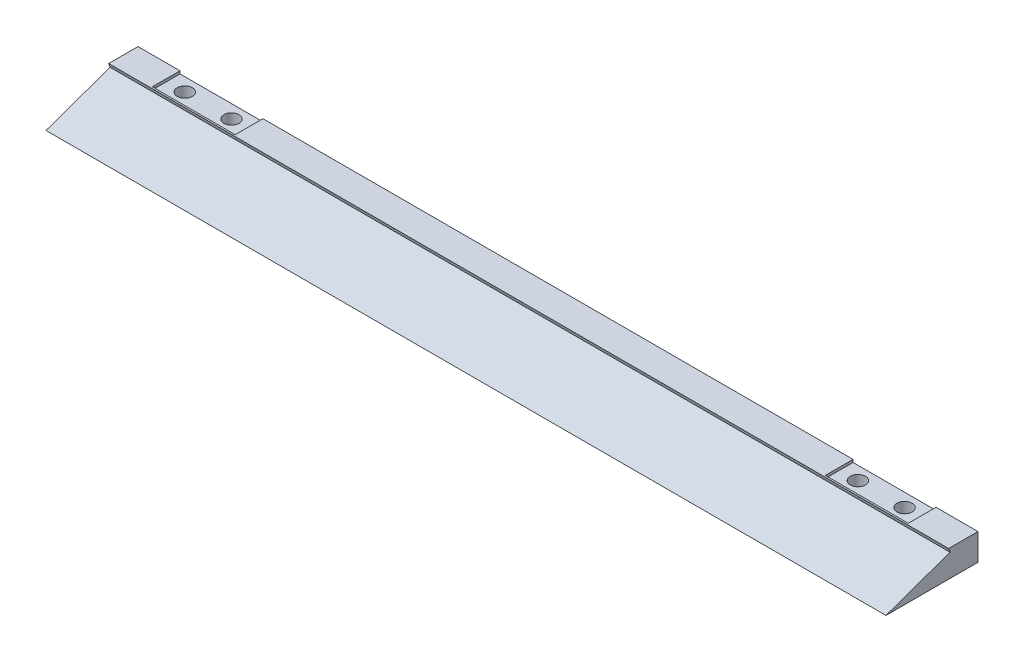
SolidWorks part; units mm, degrees
material "1023 Carbon Steel Sheet (SS)"
ref_plane "Front Plane" through (0, 0, 0) normal (0, 0, 1) x (1, 0, 0)
ref_plane "Top Plane" through (0, 0, 0) normal (0, 1, 0) x (1, 0, 0)
ref_plane "Right Plane" through (0, 0, 0) normal (1, 0, 0) x (0, 0, -1)
sketch "Sketch1" plane through (0, 0, 0) normal (0, 1, 0) x (1, 0, 0)
  line L1 (-100, -15) -> (100, -15)
  line L2 (-100, -15) -> (-100, 15)
  line L3 (-100, 15) -> (100, 15)
  line L4 (100, -15) -> (100, 15)
  line L5 (-100, -15) -> (100, 15) construction
  line L6 (-100, 15) -> (100, -15) construction
  point P0 (0, 0)
  dimension "D1" = 200
  dimension "D2" = 30
extrude "Base" add sketch "Sketch1" along normal blind 6.35
ref_plane "Midplane" through (0, 0, 0) normal (1, 0, 0) x (0, 0, -1)
sketch "Sketch2" plane through (100, 0, 0) normal (1, 0, 0) x (0, 0, -1)
  line L0 (-6.9075, 0) -> (11, 6.35)
  line L1 (-15, 0) -> (15, 0) construction
  line L2 (-15, 6.35) -> (15, 6.35) construction
  line L3 (11, 6.35) -> (11, 0)
  line L4 (11, 0) -> (-6.9075, 0)
  line L5 (15, 6.35) -> (15, 0) construction
  line L7 (11, 6.35) -> (-15, 6.35)
  line L8 (-15, 6.35) -> (-15, 0)
  line L9 (-15, 0) -> (-6.9075, 0)
  line L10 (8.3421, 5.4075) -> (8.0079, 6.35)
  line M3 (-15, 0) -> (15, 0)
  line M5 (15, 6.35) -> (-15, 6.35)
  line M6 (-15, 6.35) -> (-15, 0)
  dimension "D1" = 19
  dimension "D2" = 4
  dimension "D3" = 1
extrude "WedgeCut" cut sketch "Sketch2" against normal up to next contours L0 M3 M5 M6 region at (100, 3.7005, 5.8885)
sketch "Sketch3" plane through (0, 6.35, 0) normal (0, 1, 0) x (1, 0, 0)
  line L0 (-100, 15) -> (-100, 8.0079) construction
  line L1 (-90, 8.396) -> (-70.254, 8.396)
  line L2 (-90, 8.396) -> (-90, 15)
  line L3 (-90, 15) -> (-70.254, 15)
  line L4 (-70.254, 8.396) -> (-70.254, 15)
  line L5 (-90, 8.396) -> (-70.254, 15) construction
  line L6 (-90, 15) -> (-70.254, 8.396) construction
  line L7 (70.254, 15) -> (90, 15)
  line L8 (70.254, 15) -> (70.254, 8.396)
  line L9 (70.254, 8.396) -> (90, 8.396)
  line L10 (90, 15) -> (90, 8.396)
  line L11 (70.254, 15) -> (90, 8.396) construction
  line L12 (70.254, 8.396) -> (90, 15) construction
  line L13 (100, 15) -> (-100, 15) construction
  line L14 (100, 8.0079) -> (100, 15) construction
  point P0 (-80.127, 11.698)
  point P5 (80.127, 11.698)
  dimension "D1" = 6.604
  dimension "D2" = 19.746
  dimension "D3" = 10
  dimension "D4" = 19.746
  dimension "D5" = 10
  dimension "D6" = 6.604
extrude "Hinge Cutout" cut sketch "Sketch3" against normal blind 0.635
sketch "Sketch4" plane through (0, 5.715, 0) normal (0, 1, 0) x (1, 0, 0)
  line L0 (90, 15) -> (70.254, 15) construction
  circle A0 centre (74.5644, 11.825) radius 1.8034
  circle A1 centre (85.6896, 11.825) radius 1.8034
  point P6 (80.127, 15)
  dimension "D5" = 3.6068
  dimension "D6" = 3.6068
  dimension "D1" = 5.5626
  dimension "D2" = 5.5626
  dimension "D3" = 3.175
  dimension "D4" = 3.175
extrude "Hinge Hole Cut" cut sketch "Sketch4" against normal up to next
sketch "Sketch5" plane through (0, 0, 0) normal (0, -1, 0) x (1, 0, 0)
  line L1 (72.0394, -14.35) -> (77.0894, -14.35)
  line L2 (72.0394, -14.35) -> (72.0394, -9.3)
  line L3 (72.0394, -9.3) -> (77.0894, -9.3)
  line L4 (77.0894, -14.35) -> (77.0894, -9.3)
  line L5 (72.0394, -14.35) -> (77.0894, -9.3) construction
  line L6 (72.0394, -9.3) -> (77.0894, -14.35) construction
  line L7 (83.1646, -14.35) -> (88.2146, -14.35)
  line L8 (83.1646, -14.35) -> (83.1646, -9.3)
  line L9 (83.1646, -9.3) -> (88.2146, -9.3)
  line L10 (88.2146, -14.35) -> (88.2146, -9.3)
  line L11 (83.1646, -14.35) -> (88.2146, -9.3) construction
  line L12 (83.1646, -9.3) -> (88.2146, -14.35) construction
  point P0 (74.5644, -11.825)
  point P6 (85.6896, -11.825)
  dimension "D1" = 5.05
  dimension "D2" = 5.05
  dimension "D3" = 5.05
  dimension "D4" = 5.05
extrude "Hinge Nut Cut" cut sketch "Sketch5" against normal blind 2
mirror "Hinge Hole Mirror" about plane through (0, 0, 0) normal (1, 0, 0) of "Hinge Nut Cut", "Hinge Hole Cut"
